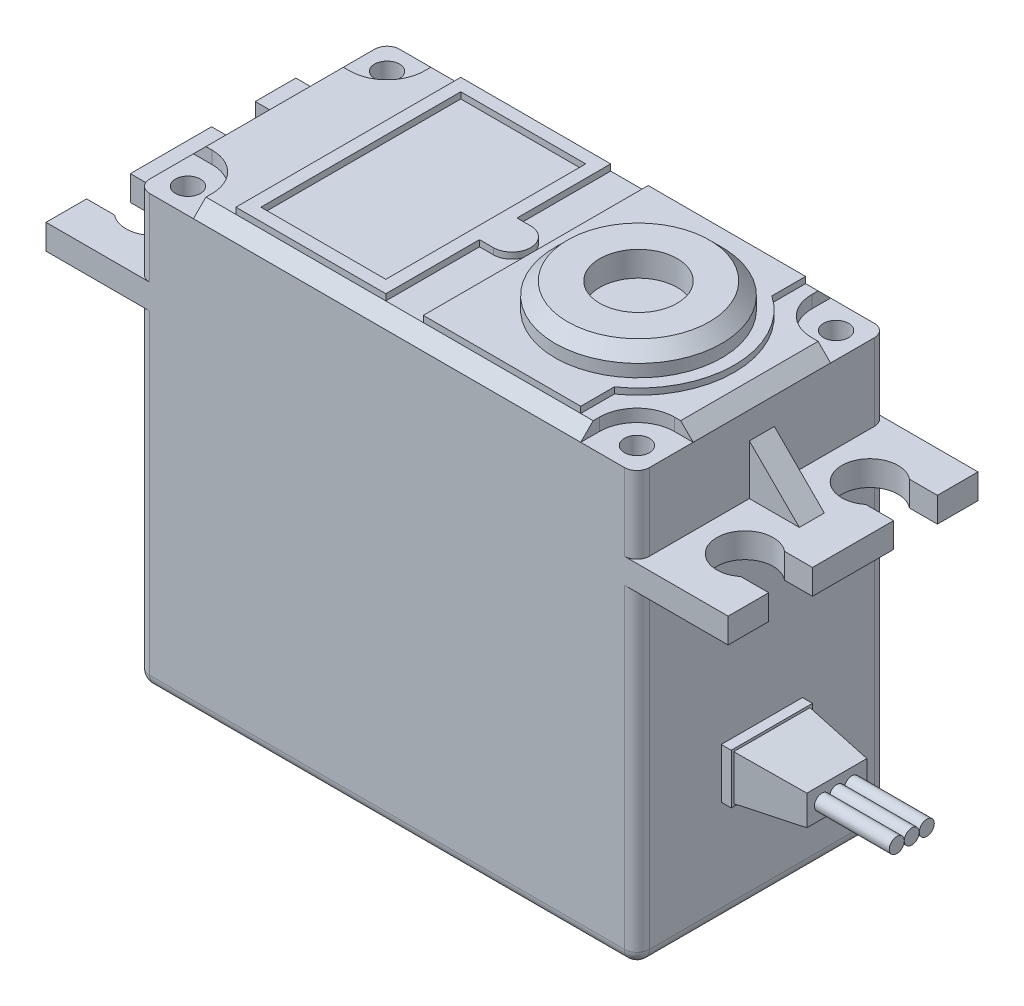
SolidWorks part; units mm, degrees
note: The reader was unsure of these and kept them because the rebuilt part matched: shared geometry of "ｽｹｯﾁ4<3>", "ｽｹｯﾁ4<5>", "ｽｹｯﾁ4<6>".
material "ABS"
ref_plane "正面" through (0, 0, 0) normal (0, 0, 1) x (1, 0, 0)
ref_plane "平面" through (0, 0, 0) normal (0, 1, 0) x (1, 0, 0)
ref_plane "右側面" through (0, 0, 0) normal (1, 0, 0) x (0, 0, -1)
sketch "ｽｹｯﾁ1" plane through (0, 0, 0) normal (0, 1, 0) x (1, 0, 0)
  line L1 (20, -10) -> (-20, -10)
  line L2 (20, -10) -> (20, 10)
  line L3 (20, 10) -> (-20, 10)
  line L4 (-20, -10) -> (-20, 10)
  line L5 (20, -10) -> (-20, 10) construction
  line L6 (20, 10) -> (-20, -10) construction
  point P0 (0, 0)
  dimension "D1" = 20
  dimension "D2" = 40
extrude "ﾎﾞｽ - 押し出し1" add sketch "ｽｹｯﾁ1" along normal blind 35.4
sketch "ｽｹｯﾁ2" plane through (0, 0, 10) normal (0, 0, 1) x (1, 0, 0)
  line L1 (20, 35.4) -> (20, 0) construction
  line L2 (20, 28.25) -> (27.3, 28.25)
  line L3 (27.3, 28.25) -> (27.3, 26.25)
  line L4 (27.3, 26.25) -> (20, 26.25)
  line L5 (20, 26.25) -> (20, 28.25)
  line L7 (-20, 35.4) -> (-20, 0) construction
  line L8 (-20, 28.25) -> (-27.3, 28.25)
  line L9 (-27.3, 28.25) -> (-27.3, 26.25)
  line L10 (-27.3, 26.25) -> (-20, 26.25)
  line L11 (-20, 26.25) -> (-20, 28.25)
extrude "ﾎﾞｽ - 押し出し2" add sketch "ｽｹｯﾁ2" against normal up to surface (20 mm away) up to face at (0, 17.7, -10)
sketch "ｽｹｯﾁ3" plane through (0, 28.25, 0) normal (0, 1, 0) x (1, 0, 0)
  line L0 (-27.3, -10) -> (-27.3, -6.75) construction
  line L1 (-27.3, 10) -> (-27.3, -10) construction
  line L2 (-27.3, -6.75) -> (-27.3, -3.25) construction
  line L3 (-27.3, -5) -> (-20, -5) construction
  line L4 (-20, 10) -> (-20, -10) construction
  line L5 (-27.3, 0) -> (-20, 0) construction
  line L6 (-27.3, 10) -> (-27.3, 6.75) construction
  line L7 (-27.3, 6.75) -> (-27.3, 3.25) construction
  line L8 (-27.3, 5) -> (-20, 5) construction
  line L9 (-27.3, -6.75) -> (-25.0642, -6.75)
  line L10 (-27.3, -3.25) -> (-25.0642, -3.25)
  line L11 (-27.3, 3.25) -> (-25.0642, 3.25)
  line L12 (-27.3, 6.75) -> (-25.0642, 6.75)
  line L13 (0, 9.669) -> (0, -9.6422) construction
  line L14 (27.3, -6.75) -> (25.0642, -6.75)
  line L15 (27.3, -3.25) -> (25.0642, -3.25)
  line L16 (27.3, 6.75) -> (25.0642, 6.75)
  line L17 (27.3, 3.25) -> (25.0642, 3.25)
  line L18 (27.3, -6.75) -> (27.3, -3.25)
  line L19 (27.3, 3.25) -> (27.3, 6.75)
  line L20 (-27.3, 3.25) -> (-27.3, 6.75)
  line L21 (-27.3, -6.75) -> (-27.3, -3.25)
  circle A0 centre (-23.65, -5) radius 2.25
  circle A1 centre (-23.65, 5) radius 2.25
  circle A2 centre (23.65, -5) radius 2.25
  circle A3 centre (23.65, 5) radius 2.25
  line M14 (-27.3, 10) -> (-27.3, -10)
  dimension "D1" = 3.25
  dimension "D2" = 3.5
extrude "ｶｯﾄ - 押し出し1" cut sketch "ｽｹｯﾁ3" against normal blind 35.4 contours A2 | L15 A2 L14 L18 | A3 | A3 L17 L19 L16 | A0 | A0 L10 L9 M14 | A1 | L11 A1 L12 M14
sketch "ｽｹｯﾁ4" plane through (0, 35.4, 0) normal (0, 1, 0) x (1, 0, 0)
  line L0 (20, 0) -> (10.125, 0) construction
  line L1 (20, -10) -> (20, 10) construction
  line L2 (20, 0) -> (19.5809, 0.5177)
  line L3 (20, 0) -> (14.5, 0) construction
  line L4 (14.5, -10) -> (1.9, -10)
  line L5 (-20, -10) -> (20, -10) construction
  line L6 (14.5, -9) -> (14.5, -6.3065)
  line L7 (-1.1, -9) -> (-1.1, 9)
  line L8 (1.9, -9) -> (1.9, 9)
  line L9 (1.9, -9) -> (14.5, -9)
  line L10 (1.9, -9) -> (-1.1, -9) construction
  line L11 (-1.1, 9) -> (-13.1, 9)
  line L12 (1.9, 9) -> (14.5, 9)
  line L13 (14.5, 9) -> (14.5, 6.3065)
  line L14 (-13.1, 9) -> (-13.1, -9)
  line L15 (-13.1, -9) -> (-1.1, -9)
  line L16 (-1.1, 0) -> (1.9, 0) construction
  line L17 (-1.1, 0) -> (0, 0) construction
  line L18 (0, 1.5) -> (-1.1, 1.5)
  line L19 (0, -1.5) -> (-1.1, -1.5)
  line L20 (-1.1, -1.5) -> (-1.1, 1.5)
  circle A0 centre (10.125, 0) radius 6.675
  arc A1 (14.5, 6.3065) -> (14.403, -6.3727) centre (10.125, 0) cw
  arc A2 (0, -1.5) -> (0, 1.5) centre (0, 0) ccw
  dimension "D2" = 5.5
  dimension "D1" = 9.875
  dimension "D3" = 12.6
extrude "ﾎﾞｽ - 押し出し3" add sketch "ｽｹｯﾁ4" along normal blind 0.5
extrude "ﾎﾞｽ - 押し出し4" add sketch "ｽｹｯﾁ4<3>" along normal blind 2.5 contours A0
sketch "ｽｹｯﾁ4<3>" plane through (0, 35.4, 0) normal (0, 1, 0) x (1, 0, 0) same geometry as "ｽｹｯﾁ4"
sketch "ｽｹｯﾁ6" plane through (0, 37.9, 0) normal (0, 1, 0) x (1, 0, 0)
  circle A0 centre (10.125, 0) radius 3
extrude "押し出し-薄板2" add sketch "ｽｹｯﾁ4<5>" along normal blind 0.5 thin contours L14 L15 L7 L11
sketch "ｽｹｯﾁ4<5>" plane through (0, 35.4, 0) normal (0, 1, 0) x (1, 0, 0) same geometry as "ｽｹｯﾁ4"
extrude "ﾎﾞｽ - 押し出し6" add sketch "ｽｹｯﾁ4<6>" along normal up to surface (0.5 mm away) contours L19 A2 L18 L7 up to face at (-7.1, 35.9, 0)
sketch "ｽｹｯﾁ4<6>" plane through (0, 35.4, 0) normal (0, 1, 0) x (1, 0, 0) same geometry as "ｽｹｯﾁ4"
sketch "ｽｹｯﾁ13" plane through (20, 0, 0) normal (1, 0, 0) x (0, 0, -1)
  line L0 (0, 0) -> (0, 10.3305) construction
  line L1 (-3.25, 12.3305) -> (3.25, 12.3305)
  line L2 (-3.25, 12.3305) -> (-3.25, 8.3305)
  line L3 (-3.25, 8.3305) -> (3.25, 8.3305)
  line L4 (3.25, 12.3305) -> (3.25, 8.3305)
  line L5 (-3.25, 12.3305) -> (3.25, 8.3305) construction
  line L6 (-3.25, 8.3305) -> (3.25, 12.3305) construction
extrude "ﾎﾞｽ - 押し出し8" add sketch "ｽｹｯﾁ13" along normal blind 6
sketch "ｽｹｯﾁ14" plane through (0, 0, 3.25) normal (0, 0, 1) x (1, 0, 0)
  line L1 (20, 8.3305) -> (20.8, 8.3305)
  line L2 (20, 8.3305) -> (20, 12.3305)
  line L3 (20, 12.3305) -> (20.8, 12.3305)
  line L4 (20.8, 8.5305) -> (26, 9.1305)
  line L5 (26, 10.3305) -> (26, 11.5305) construction
  line L7 (20.8, 12.3305) -> (20.8, 12.1305)
  line L8 (26, 11.5305) -> (26, 9.1305)
  line L9 (26, 10.3305) -> (20, 10.3305) construction
  line L10 (20.8, 8.3305) -> (20.8, 8.5305)
  line L11 (20.8, 12.1305) -> (20.8, 8.5305)
  line L12 (20.8, 12.1305) -> (26, 11.5305)
  line L13 (26, 9.1305) -> (26, 8.3305)
  line L14 (26, 8.3305) -> (20.8, 8.3305)
  line L15 (26, 11.5305) -> (26, 12.3305)
  line L16 (26, 12.3305) -> (20.8, 12.3305)
  point P16 (20.8, 10.3305)
  line M25 (20, 8.3305) -> (26, 8.3305)
  line M26 (26, 8.3305) -> (26, 12.3305)
  line M27 (26, 12.3305) -> (20, 12.3305)
  dimension "D1" = 0.8
extrude "ｶｯﾄ - 押し出し5" cut sketch "ｽｹｯﾁ14" against normal through all contours L10 L4 M25 M26 | L7 L12 M26 M27
sketch "ｽｹｯﾁ15" plane through (0, 8.3305, 0) normal (0, -1, 0) x (1, 0, 0)
  line L0 (20.8, -3.25) -> (20.8, -3.05)
  line L2 (20.8, 0) -> (26, 0) construction
  line L3 (26, 0) -> (26, -2.4)
  line L4 (26, -2.4) -> (20.8, -3.05)
  line L5 (20.8, -3.25) -> (26, -3.25)
  line L6 (26, -2.4) -> (26, -3.25)
  line L7 (20.8, 3.25) -> (20.8, 3.05)
  line L8 (26, 2.4) -> (26, 3.25)
  line L9 (26, 2.4) -> (20.8, 3.05)
  line L10 (20.8, 3.25) -> (26, 3.25)
  line M16 (20.8, -3.25) -> (20.8, 3.25)
extrude "ｶｯﾄ - 押し出し6" cut sketch "ｽｹｯﾁ15" against normal blind 6 contours L10 L9 L8 M16 | L6 L4 L5 M16
sketch "ｽｹｯﾁ17" plane through (26, 0, 0) normal (1, 0, 0) x (0, 0, -1)
  line L0 (0, 11.5305) -> (0, 9.1305) construction
  line L1 (2.4, 11.5305) -> (-2.4, 11.5305) construction
  line L2 (-2.4, 9.1305) -> (2.4, 9.1305) construction
  line L3 (0, 10.3305) -> (-2.4, 10.3305) construction
  line L4 (-2.4, 11.5305) -> (-2.4, 9.1305) construction
  line L5 (0, 10.3305) -> (2.4, 10.3305) construction
  line L6 (2.4, 11.5305) -> (2.4, 9.1305) construction
  circle A0 centre (0, 10.3305) radius 0.6
  circle A1 centre (1.2, 10.3305) radius 0.6
  circle A2 centre (-1.2, 10.3305) radius 0.6
extrude "ﾎﾞｽ - 押し出し11" add sketch "ｽｹｯﾁ17" along normal blind 6 separate body contours A2 | A0 | A1
sketch "ｽｹｯﾁ18" plane through (-20, 0, 0) normal (-1, 0, 0) x (0, 0, 1)
  line L0 (-1, 28.25) -> (1, 28.25)
  line L1 (-10, 28.25) -> (10, 28.25) construction
  line L2 (0, 28.25) -> (0, 35.4) construction
  line L3 (-10, 35.4) -> (10, 35.4) construction
  line L4 (1, 28.25) -> (1, 32.25)
  line L5 (1, 32.25) -> (-1, 32.25)
  line L6 (-1, 28.25) -> (-1, 32.25)
  point P11 (0, 32.25)
extrude "ﾎﾞｽ - 押し出し12" add sketch "ｽｹｯﾁ18" along normal blind 4
sketch "ｽｹｯﾁ19" plane through (0, 0, -1) normal (0, 0, -1) x (-1, 0, 0)
  line L0 (24, 28.25) -> (20, 32.25)
  line L1 (20, 32.25) -> (24, 32.25)
  line L2 (24, 32.25) -> (24, 28.25)
extrude "ｶｯﾄ - 押し出し7" cut sketch "ｽｹｯﾁ19" against normal blind 4
sketch "ｽｹｯﾁ20" plane through (0, 0, -10) normal (0, 0, -1) x (-1, 0, 0)
  line L0 (0, 0.5414) -> (0, 35.4) construction
  line L1 (-20, 35.4) -> (20, 35.4) construction
ref_plane "平面4" through (0, 0, 0) normal (-1, 0, 0) x (0, 1, 0)
mirror "ﾐﾗｰ5" about plane through (0, 0, 0) normal (-1, 0, 0) of "ﾎﾞｽ - 押し出し1", "ﾎﾞｽ - 押し出し12", "ｶｯﾄ - 押し出し7"
chamfer "面取り2" distance 1 angle 45 1 edges at (10.125, 37.9, 6.675)
sketch "ｽｹｯﾁ21" plane through (0, 37.9, 0) normal (0, 1, 0) x (1, 0, 0)
  circle A0 centre (10.125, 0) radius 3.1
extrude "ｶｯﾄ - 押し出し8" cut sketch "ｽｹｯﾁ21" against normal blind 2
sketch "ｽｹｯﾁ23" plane through (0, 35.4, 0) normal (0, 1, 0) x (1, 0, 0)
  line L0 (-20, -10) -> (-15.5, -10)
  line L1 (-20, -10) -> (20, -10) construction
  line L2 (-15.5, -10) -> (-15.5, -5.5)
  line L3 (-15.5, -5.5) -> (-20, -5.5)
  line L4 (-20, 10) -> (-20, -10) construction
  line L5 (-20, -5.5) -> (-20, -10)
  line L6 (-20, 5.5) -> (-15.5, 5.5)
  line L7 (-20, 10) -> (-20, 5.5)
  line L8 (-15.5, 10) -> (-20, 10)
  line L9 (-15.5, 5.5) -> (-15.5, 10)
  line L10 (15.5, 5.5) -> (20, 5.5)
  line L11 (20, 5.5) -> (20, 10)
  line L12 (15.5, 10) -> (15.5, 5.5)
  line L13 (20, 10) -> (15.5, 10)
  line L14 (15.5, -10) -> (20, -10)
  line L15 (20, -10) -> (20, -5.5)
  line L16 (20, -5.5) -> (15.5, -5.5)
  line L17 (15.5, -5.5) -> (15.5, -10)
extrude "ｶｯﾄ - 押し出し9" cut sketch "ｽｹｯﾁ23" against normal blind 1
fillet "ﾌｨﾚｯﾄ3" radius 3 4 edges at (15.5, 34.9, 5.5) (15.5, 34.9, -5.5) (-15.5, 34.9, 5.5) (-15.5, 34.9, -5.5)
sketch "ｽｹｯﾁ24" plane through (0, 34.4, 0) normal (0, 1, 0) x (1, 0, 0)
  line L0 (-15.5, 8.5) -> (-20, 8.5) construction
  line L1 (-16.3787, 6.3787) -> (-18.5, 8.5) construction
  line L2 (-18.5, 5.5) -> (-18.5, 10) construction
  line L3 (-18.5, -5.5) -> (-18.5, -10) construction
  line L4 (-15.5, -8.5) -> (-20, -8.5) construction
  line L5 (-16.3787, -6.3787) -> (-18.5, -8.5) construction
  line L6 (18.5, 5.5) -> (18.5, 10) construction
  line L7 (15.5, 8.5) -> (20, 8.5) construction
  line L8 (15.5, -8.5) -> (20, -8.5) construction
  line L9 (18.5, -5.5) -> (18.5, -10) construction
  line L10 (16.3787, -6.3787) -> (18.5, -8.5) construction
  line L11 (16.3787, 6.3787) -> (18.5, 8.5) construction
  circle A0 centre (-17.9697, 7.9697) radius 1
  circle A1 centre (-17.9697, -7.9697) radius 1
  circle A2 centre (17.9697, -7.9697) radius 1
  circle A3 centre (17.9697, 7.9697) radius 1
extrude "ｶｯﾄ - 押し出し10" cut sketch "ｽｹｯﾁ24" against normal blind 2
chamfer "面取り3" distance 1 angle 45 4 edges at (20, 35.4, 0) (0, 35.4, 10) (-20, 35.4, 0) (0, 35.4, -10)
fillet "ﾌｨﾚｯﾄ6" radius 1 8 edges
fillet "ﾌｨﾚｯﾄ7" radius 1 8 edges at (19.7071, 0, 9.7071) (20, 0, 0) (19.7071, 0, -9.7071) (0, 0, -10) (-19.7071, 0, -9.7071) (0, 0, 10) (-19.7071, 0, 9.7071) (-20, 0, 0)
